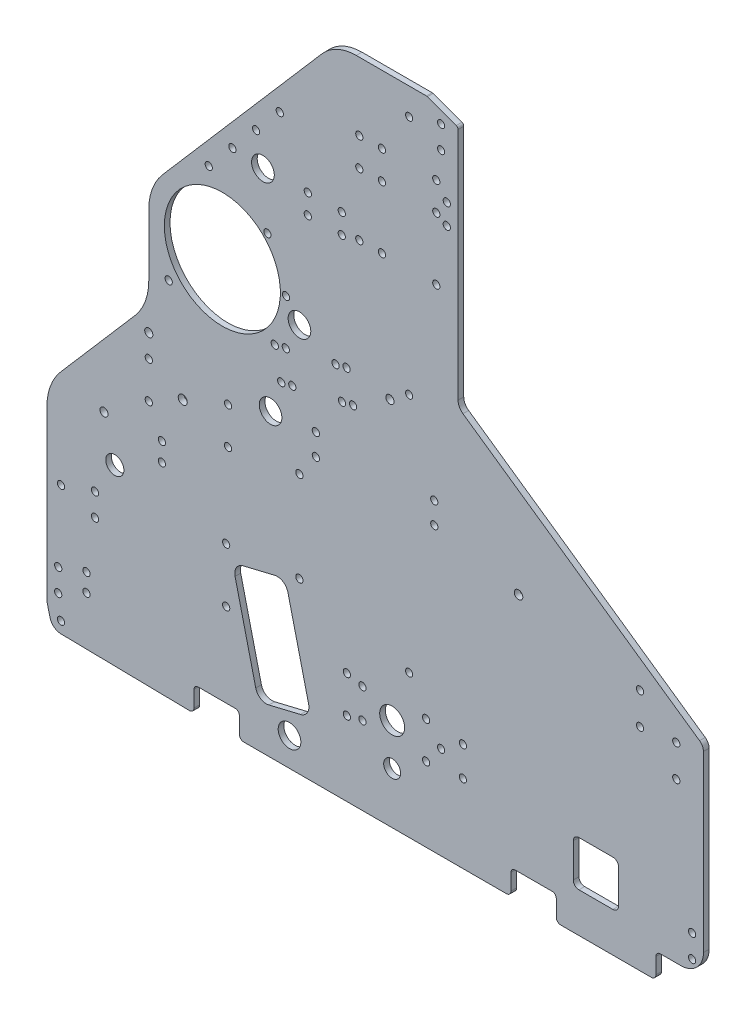
SolidWorks part; units mm, degrees
ref_plane "Front Plane" through (0, 0, 0) normal (0, 0, 1) x (1, 0, 0)
ref_plane "Top Plane" through (0, 0, 0) normal (0, 1, 0) x (1, 0, 0)
ref_plane "Right Plane" through (0, 0, 0) normal (1, 0, 0) x (0, 0, -1)
sketch "Sketch1" plane through (0, 0, 0) normal (0, 0, 1) x (1, 0, 0)
  line L0 (82.55, -20.32) -> (82.55, -6.35)
  line L2 (0, 0) -> (0, 157.48)
  line L4 (368.3, -20.32) -> (368.3, 106.68)
  line L5 (82.55, -6.35) -> (107.95, -6.35)
  line L6 (107.95, -6.35) -> (107.95, -20.32)
  line L7 (107.95, -20.32) -> (260.35, -20.32)
  line L8 (260.35, -20.32) -> (260.35, -6.35)
  line L9 (260.35, -6.35) -> (285.75, -6.35)
  line L10 (285.75, -6.35) -> (285.75, -20.32)
  line L11 (285.75, -20.32) -> (368.3, -20.32)
  line L12 (361.95, 12.7) -> (368.3, 12.7) construction
  line L13 (0, 0) -> (6.35, 0) construction
  line L14 (0.1896, -7.8901) -> (1.7771, -14.2401)
  line L15 (7.8295, -19.0491) -> (82.55, -20.32)
  line L16 (0, 0) -> (0, -6.35)
  line L17 (76.2, 128.905) -> (79.375, 128.905) construction
  line L18 (57.15, 118.5863) -> (101.6, 118.5862) construction
  line L19 (57.15, 118.5863) -> (57.15, 139.2238) construction
  line L20 (101.6, 118.5862) -> (101.6, 139.2237) construction
  line L21 (57.15, 139.2238) -> (101.6, 139.2237) construction
  line L22 (57.15, 118.5863) -> (101.6, 139.2237) construction
  line L23 (101.6, 118.5862) -> (57.15, 139.2238) construction
  line L24 (101.6, 139.2237) -> (125.4682, 147.9111) construction
  line L25 (203.2, 59.805) -> (203.2, 194.805) construction
  line L26 (203.2, 194.805) -> (203.2, 329.805) construction
  line L27 (355.6, 332.105) -> (330.2, 332.105) construction
  line L28 (330.2, 332.105) -> (330.2, 217.805) construction
  line L29 (330.2, 217.805) -> (355.6, 217.805) construction
  line L30 (355.6, 217.805) -> (355.6, 332.105) construction
  line L31 (203.2, 344.805) -> (203.2, 194.805) construction
  line L32 (50.8, 332.105) -> (76.2, 332.105) construction
  line L33 (76.2, 332.105) -> (76.2, 217.805) construction
  line L34 (50.8, 217.805) -> (50.8, 332.105) construction
  line L35 (76.2, 217.805) -> (50.8, 217.805) construction
  line L36 (213.2, 344.805) -> (230.6638, 338.455)
  line L37 (203.2, 344.805) -> (161.925, 344.805)
  line L38 (203.2, 344.805) -> (213.2, 344.805)
  line L39 (348.5362, 344.805) -> (413.4623, 344.805)
  line L40 (348.5362, 344.805) -> (230.6638, 344.805) construction
  line L42 (161.925, 344.805) -> (0, 157.48)
  line L44 (230.6638, 338.455) -> (230.6638, 202.565)
  line L45 (230.6638, 202.565) -> (368.3, 106.68)
  line L46 (213.2, 344.805) -> (-141.0713, 344.805) construction
  circle A0 centre (6.35, 0) radius 2.032
  circle A1 centre (6.35, 12.7) radius 2.032
  circle A2 centre (361.95, 0) radius 2.032
  circle A3 centre (361.95, 12.7) radius 2.032
  arc A5 (1.7771, -14.2401) -> (7.8295, -19.0491) centre (7.9375, -12.7) ccw
  circle A6 centre (7.9375, -12.7) radius 2.032
  arc A7 (0, -6.35) -> (0.1896, -7.8901) centre (6.35, -6.35) ccw
  circle A8 centre (38.1, 78.105) radius 5.08
  circle A9 centre (76.2, 128.905) radius 2.54
  circle A10 centre (101.6, 118.5862) radius 2.032
  circle A11 centre (101.6, 139.2237) radius 2.032
  circle A12 centre (57.15, 139.2238) radius 2.032
  circle A13 centre (57.15, 118.5863) radius 2.032
  circle A15 centre (203.2, 59.805) radius 2
  circle A16 centre (203.2, 194.805) radius 2
  circle A17 centre (203.2, 329.805) radius 2
  circle A18 centre (63.5, 313.055) radius 2.032
  circle A20 centre (355.6, 332.105) radius 2.032
  circle A21 centre (330.2, 332.105) radius 2.032
  circle A22 centre (355.6, 217.805) radius 2.032
  circle A23 centre (330.2, 217.805) radius 2.032
  circle A24 centre (50.8, 332.105) radius 2.032
  circle A25 centre (76.2, 332.105) radius 2.032
  circle A26 centre (50.8, 217.805) radius 2.032
  circle A27 centre (76.2, 217.805) radius 2.032
  circle A28 centre (221.1381, 335.28) radius 2
  circle A29 centre (224.3138, 298.831) radius 2.032
  circle A30 centre (353.06, 100.7351) radius 2.032
  circle A31 centre (332.74, 115.9751) radius 2.032
  circle A32 centre (332.74, 98.1951) radius 2.032
  circle A33 centre (353.06, 82.9551) radius 2.032
  circle A34 centre (117.3562, 280.4276) radius 2.032
  circle A35 centre (104.0678, 265.0548) radius 2.032
  circle A36 centre (90.7795, 249.682) radius 2.032
  circle A38 centre (130.6445, 295.8004) radius 2.032
  circle A39 centre (68.326, 182.9237) radius 2.032
  circle A40 centre (224.3138, 287.401) radius 2.032
  circle A41 centre (125.4682, 147.9111) radius 6.35
  circle A42 centre (221.1381, 322.58) radius 2
  point P82 (203.2, 344.805)
  point P90 (368.3, 62.484)
  point P106 (0, 0)
  dimension "D6" = 4.064
  dimension "D10" = 6.35
  dimension "D11" = 4.064
  dimension "D17" = 38.1
  dimension "D27" = 4
  dimension "D31" = 4.064
  dimension "D32" = 41.275
  dimension "D36" = 4.064
  dimension "D47" = 39.624
  dimension "D48" = 4.064
  dimension "D25" = 5.08
  dimension "D26" = 4.064
  dimension "D52" = 4.064
  dimension "D65" = 4.064
  dimension "D69" = 10.16
  dimension "D72" = 12.7
  dimension "D2" = 127
  dimension "D3" = 13.97
  dimension "D4" = 25.4
  dimension "D5" = 152.4
  dimension "D7" = 12.7
  dimension "D8" = 6.35
  dimension "D9" = 20.32
  dimension "D12" = 12.7
  dimension "D13" = 1.5875
  dimension "D14" = 82.55
  dimension "D15" = 368.3
  dimension "D16" = 6.35
  dimension "D18" = 98.425
  dimension "D19" = 38.1
  dimension "D20" = 50.8
  dimension "D21" = 3.175
  dimension "D22" = 270
  dimension "D23" = 20.6375
  dimension "D24" = 44.45
  dimension "D28" = 135
  dimension "D29" = 12.7
  dimension "D30" = 15
  dimension "D33" = 63.5
  dimension "D34" = 27.4638
  dimension "D35" = 12.7
  dimension "D37" = 114.3
  dimension "D38" = 25.4
  dimension "D39" = 12.7
  dimension "D40" = 157.48
  dimension "D41" = 142.24
  dimension "D42" = 365.125
  dimension "D43" = 10
  dimension "D44" = 6.35
  dimension "D45" = 31.75
  dimension "D46" = 3.175
  dimension "D49" = 6.35
  dimension "D50" = 203.2
  dimension "D51" = 15.24
  dimension "D53" = 17.78
  dimension "D54" = 17.78
  dimension "D55" = 20.32
  dimension "D56" = 15.24
  dimension "D57" = 92.202
  dimension "D58" = 8.382
  dimension "D59" = 20.32
  dimension "D60" = 20.32
  dimension "D61" = 8.382
  dimension "D62" = 20.32
  dimension "D63" = 8.382
  dimension "D64" = 8.382
  dimension "D66" = 35.052
  dimension "D67" = 68.326
  dimension "D68" = 11.43
  dimension "D70" = 25.4
  dimension "D71" = 110
  dimension "D73" = 17.9381
  dimension "D74" = 12.7
extrude "Boss-Extrude1" add sketch "Sketch1" along normal blind 3.175 contours L16 A7 L14 A5 L15 L2 A0 A1 A6 region at (171.5045, 119.4976, 0)
fillet "Fillet1" radius 2.286 4 edges at (285.75, -6.35, 1.5875) (107.95, -6.35, 1.5875) (260.35, -6.35, 1.5875) (82.55, -6.35, 1.5875)
fillet "Fillet2" radius 6.35 1 edges at (230.6638, 202.565, 1.5875)
sketch "Sketch2" plane through (0, 0, 0) normal (0, 0, -1) x (-1, 0, 0)
  circle A0 centre (-100.5528, 71.086) radius 2.032 construction
  circle A1 centre (-100.5528, 40.606) radius 2.032 construction
  circle A2 centre (-22.225, 18.2025) radius 2.032 construction
  circle A3 centre (-22.225, 8.0425) radius 2.032 construction
  circle A4 centre (-100.5528, 71.086) radius 2.032
  circle A5 centre (-100.5528, 40.606) radius 2.032
  circle A6 centre (-22.225, 18.2025) radius 2.032
  circle A7 centre (-22.225, 8.0425) radius 2.032
extrude "Cut-Extrude1" cut sketch "Sketch2" against normal through all
fillet "Fillet3" radius 1.5875 2 edges at (230.6638, 338.455, 1.5875) (213.2, 344.805, 1.5875)
sketch "Sketch3" plane through (0, 0, 3.175) normal (0, 0, 1) x (1, 0, 0)
  line L0 (132.9524, 63.2646) -> (132.7215, 64.2281) construction
  line L1 (128.3814, 66.8897) -> (110.6828, 62.6472) construction
  line L2 (114.5132, 58.4237) -> (126.8822, 61.3887) construction
  line L3 (108.0212, 58.3071) -> (108.2522, 57.3436) construction
  line L4 (131.2006, 57.703) -> (140.0164, 20.9265) construction
  line L5 (144.0993, 16.7636) -> (132.9524, 63.2646) construction
  line L6 (108.2522, 57.3436) -> (119.3991, 10.8426) construction
  line L7 (121.1509, 16.4042) -> (112.3351, 53.1807) construction
  line L8 (119.3991, 10.8426) -> (119.6301, 9.8791) construction
  line L9 (144.3303, 15.8001) -> (144.0993, 16.7636) construction
  line L10 (137.8383, 15.6835) -> (125.4694, 12.7185) construction
  line L11 (123.9701, 7.2175) -> (141.6687, 11.4601) construction
  line L12 (132.9524, 63.2646) -> (132.7215, 64.2281)
  line L13 (128.3814, 66.8897) -> (110.6828, 62.6472)
  line L14 (114.5132, 58.4237) -> (126.8822, 61.3887)
  line L15 (108.0212, 58.3071) -> (108.2522, 57.3436)
  line L16 (131.2006, 57.703) -> (140.0164, 20.9265)
  line L17 (144.0993, 16.7636) -> (132.9524, 63.2646)
  line L18 (108.2522, 57.3436) -> (119.3991, 10.8426)
  line L19 (121.1509, 16.4042) -> (112.3351, 53.1807)
  line L20 (119.3991, 10.8426) -> (119.6301, 9.8791)
  line L21 (144.3303, 15.8001) -> (144.0993, 16.7636)
  line L22 (137.8383, 15.6835) -> (125.4694, 12.7185)
  line L23 (123.9701, 7.2175) -> (141.6687, 11.4601)
  line L24 (127.7894, 69.3598) -> (110.0908, 65.1172)
  line L25 (105.5512, 57.715) -> (105.7822, 56.7515)
  line L26 (105.7822, 56.7515) -> (116.9291, 10.2505)
  line L27 (116.9291, 10.2505) -> (117.16, 9.287)
  line L28 (124.5622, 4.7475) -> (142.2608, 8.99)
  line L29 (146.8003, 16.3922) -> (146.5694, 17.3557)
  line L30 (146.5694, 17.3557) -> (135.4225, 63.8567)
  line L31 (135.4225, 63.8567) -> (135.1915, 64.8202)
  line L32 (14.605, -0.1369) -> (103.7278, 32.3011) construction
  line L33 (14.605, -0.1369) -> (103.7278, 32.3011)
  line L34 (0, -6.35) -> (0, 157.48) construction
  line L35 (-39.6666, 74.7152) -> (103.7278, 126.9065) construction
  line L36 (26.9875, 46.9531) -> (26.9875, 59.6531) construction
  line L37 (107.95, -20.32) -> (260.35, -20.32) construction
  line L38 (64.5259, 92.5258) -> (64.5259, 102.9405) construction
  line L39 (131.6538, 14.201) -> (136.0946, -4.3242) construction
  arc A0 (132.7215, 64.2281) -> (128.6308, 66.9403) centre (129.2206, 63.3889) ccw construction
  arc A1 (110.6828, 62.6472) -> (110.4377, 62.5791) centre (111.522, 59.1463) ccw construction
  arc A2 (128.6308, 66.9403) -> (128.3814, 66.8897) centre (129.2206, 63.3889) ccw construction
  arc A3 (110.4377, 62.5791) -> (108.0212, 58.3071) centre (111.522, 59.1463) ccw construction
  arc A4 (119.6301, 9.8791) -> (123.7207, 7.1669) centre (123.1309, 10.7183) ccw construction
  arc A5 (141.9139, 11.5281) -> (144.3303, 15.8001) centre (140.8295, 14.9609) ccw construction
  arc A6 (141.6687, 11.4601) -> (141.9139, 11.5281) centre (140.8295, 14.9609) ccw construction
  arc A7 (123.7207, 7.1669) -> (123.9701, 7.2175) centre (123.1309, 10.7183) ccw construction
  arc A8 (132.7215, 64.2281) -> (128.6308, 66.9403) centre (129.2206, 63.3889) ccw
  arc A9 (110.6828, 62.6472) -> (110.4377, 62.5791) centre (111.522, 59.1463) ccw
  arc A10 (128.6308, 66.9403) -> (128.3814, 66.8897) centre (129.2206, 63.3889) ccw
  arc A11 (110.4377, 62.5791) -> (108.0212, 58.3071) centre (111.522, 59.1463) ccw
  arc A12 (119.6301, 9.8791) -> (123.7207, 7.1669) centre (123.1309, 10.7183) ccw
  arc A13 (141.9139, 11.5281) -> (144.3303, 15.8001) centre (140.8295, 14.9609) ccw
  arc A14 (141.6687, 11.4601) -> (141.9139, 11.5281) centre (140.8295, 14.9609) ccw
  arc A15 (123.7207, 7.1669) -> (123.9701, 7.2175) centre (123.1309, 10.7183) ccw
  arc A16 (110.0908, 65.1172) -> (109.6726, 65.0012) centre (111.522, 59.1463) ccw
  arc A17 (109.6726, 65.0012) -> (105.5512, 57.715) centre (111.522, 59.1463) ccw
  arc A18 (117.16, 9.287) -> (124.1369, 4.6613) centre (123.1309, 10.7183) ccw
  arc A19 (124.1369, 4.6613) -> (124.5622, 4.7475) centre (123.1309, 10.7183) ccw
  arc A20 (142.2608, 8.99) -> (142.6789, 9.1061) centre (140.8295, 14.9609) ccw
  arc A21 (142.6789, 9.1061) -> (146.8003, 16.3922) centre (140.8295, 14.9609) ccw
  arc A22 (135.1915, 64.8202) -> (128.2147, 69.446) centre (129.2206, 63.3889) ccw
  arc A23 (128.2147, 69.446) -> (127.7894, 69.3598) centre (129.2206, 63.3889) ccw
  circle A24 centre (136.0946, -4.3242) radius 6.35
  circle A26 centre (134.1437, 208.2281) radius 2.032 construction
  circle A33 centre (26.9875, 46.9531) radius 2.032
  circle A34 centre (26.9875, 59.6531) radius 2.032
  circle A35 centre (7.9375, 53.3031) radius 2.032
  circle A37 centre (32.0306, 100.8109) radius 32.385 construction
  circle A38 centre (32.0306, 100.8109) radius 2.286
  circle A39 centre (123.682, 233.4851) radius 2.032 construction
  circle A40 centre (64.5259, 102.9405) radius 2.032
  circle A41 centre (64.5259, 92.5258) radius 2.032
  circle A42 centre (134.1437, 208.2281) radius 2.032
  circle A43 centre (123.682, 233.4851) radius 2.032
  ellipse E0 centre (124.5974, 48.8487) end of major axis (128.5376, 61.3578) minor radius 6 (131.2006, 57.703) -> (126.8822, 61.3887) ccw construction
  ellipse E1 centre (122.2349, 48.2824) end of major axis (113.0518, 57.6456) minor radius 6 (114.5132, 58.4237) -> (112.3351, 53.1807) ccw construction
  ellipse E2 centre (127.7541, 25.2585) end of major axis (131.6942, 37.7675) minor radius 6 (121.1509, 16.4042) -> (125.4694, 12.7185) ccw construction
  ellipse E3 centre (130.1166, 25.8248) end of major axis (139.2998, 16.4616) minor radius 6 (137.8383, 15.6835) -> (140.0164, 20.9265) ccw construction
  ellipse E4 centre (124.5974, 48.8487) end of major axis (120.6573, 36.3397) minor radius 6 (131.2006, 57.703) -> (126.8822, 61.3887) ccw
  ellipse E5 centre (122.2349, 48.2824) end of major axis (131.4181, 38.9192) minor radius 6 (114.5132, 58.4237) -> (112.3351, 53.1807) ccw
  ellipse E6 centre (127.7541, 25.2585) end of major axis (131.6942, 37.7675) minor radius 6 (121.1509, 16.4042) -> (125.4694, 12.7185) ccw
  ellipse E7 centre (130.1166, 25.8248) end of major axis (139.2998, 16.4616) minor radius 6 (137.8383, 15.6835) -> (140.0164, 20.9265) ccw
  point P93 (26.9875, 53.3031)
  point P115 (32.0306, 100.8109)
  dimension "D3" = 64.77
  dimension "D4" = 4.572
  dimension "D8" = 4.064
  dimension "D13" = 12.7
  dimension "D2" = 88.9
  dimension "D5" = 7.9375
  dimension "D6" = 19.05
  dimension "D7" = 73.6231
  dimension "D9" = 12.7
  dimension "D10" = 10.4147
  dimension "D11" = 37.5384
  dimension "D12" = 45.5727
  dimension "D14" = 19.05
  dimension "D1" = 2.54
extrude "Cut-Extrude2" cut sketch "Sketch3" against normal through all contours A22 A23 L24 A16 A17 L25 L26 L27 A18 A19 L28 A20 A21 L29 L30 L31 A15 A12 L20 L18 L15 A11 A9 L13 A10 A8 L12 L17 L21 A13 A14 L23 | A12 A15 L23 A14 A13 L21 L17 L12 A8 A10 L13 A9 A11 L15 L18 L20 E7 L22 E6 L19 E5 L14 E4 L16 | L22 E7 L16 E4 L14 E5 L19 E6 | A38 | A41 | A40 | A35 | A34 | A33 | A43 | A42 | A24 region at (137.844, 39.8506, 3.175) region at (126.1758, 37.0536, 3.175) region at (128.1544, 68.6507, 3.175) region at (32.0306, 100.8109, 3.175) region at (64.5259, 102.9405, 3.175) region at (64.5259, 92.5258, 3.175)
sketch "Sketch4" plane through (0, 0, 3.175) normal (0, 0, 1) x (1, 0, 0)
  line L0 (57.15, 139.2238) -> (101.6, 139.2237) construction
  line L1 (168.275, 21.4312) -> (212.725, 21.4312) construction
  line L2 (168.275, 21.4312) -> (168.275, 42.0687) construction
  line L3 (168.275, 42.0687) -> (212.725, 42.0687) construction
  line L4 (212.725, 21.4312) -> (212.725, 42.0687) construction
  line L5 (168.275, 21.4312) -> (212.725, 42.0687) construction
  line L6 (168.275, 42.0687) -> (212.725, 21.4312) construction
  line L7 (57.15, 118.5863) -> (57.15, 139.2238) construction
  line L8 (107.95, -20.32) -> (260.35, -20.32) construction
  line L9 (193.675, 31.75) -> (177.005, 31.75) construction
  line L10 (190.5, 31.75) -> (193.675, 31.75) construction
  line L11 (6.35, 12.7) -> (361.95, 12.7) construction
  line L12 (107.95, -6.35) -> (107.95, -20.32) construction
  line L13 (193.675, 31.75) -> (220.6625, 31.75) construction
  line L14 (177.005, 23.4569) -> (177.005, 40.0431) construction
  line L15 (213.2, 44.805) -> (193.2, 44.805) construction
  line L16 (213.2, 44.805) -> (213.2, 344.805) construction
  line L17 (213.2, 344.805) -> (193.2, 344.805) construction
  line L18 (193.2, 44.805) -> (193.2, 344.805) construction
  line L19 (213.2, 44.805) -> (193.2, 344.805) construction
  line L20 (213.2, 344.805) -> (193.2, 44.805) construction
  line L21 (226.1381, 335.28) -> (226.1381, 31.75) construction
  line L22 (237.33, 40.0431) -> (233.3612, 40.0431) construction
  line L23 (237.33, 23.4569) -> (233.3612, 23.4569) construction
  circle A0 centre (168.275, 42.0687) radius 2.032
  circle A1 centre (212.725, 42.0687) radius 2.032
  circle A2 centre (212.725, 21.4312) radius 2.032
  circle A3 centre (168.275, 21.4312) radius 2.032
  circle A4 centre (193.675, 31.75) radius 6.985
  circle A7 centre (220.6625, 31.75) radius 14.2875 construction
  circle A8 centre (193.675, 31.75) radius 12.7 construction
  circle A9 centre (177.005, 40.0431) radius 2.032
  circle A10 centre (177.005, 23.4569) radius 2.032
  circle A11 centre (237.33, 40.0431) radius 2.032 construction
  circle A12 centre (237.33, 23.4569) radius 2.032 construction
  circle A13 centre (193.675, 8.4667) radius 4.7625
  circle A14 centre (221.1381, 31.75) radius 2.032
  circle A15 centre (221.1381, 31.75) radius 5 construction
  circle A16 centre (221.1381, 335.28) radius 5 construction
  circle A17 centre (233.3612, 23.4569) radius 2.032
  circle A18 centre (233.3612, 40.0431) radius 2.032
  point P0 (190.5, 31.75)
  point P26 (203.2, 194.805)
  point P38 (177.005, 31.75)
  dimension "D1" = 4.064
  dimension "D4" = 13.97
  dimension "D7" = 9.525
  dimension "D10" = 25.4
  dimension "D11" = 28.575
  dimension "D16" = 10
  dimension "D17" = 4.064
  dimension "D18" = 10
  dimension "D2" = 52.07
  dimension "D3" = 3.175
  dimension "D5" = 82.55
  dimension "D6" = 26.9875
  dimension "D8" = 20
  dimension "D9" = 300
  dimension "D12" = 16.67
  dimension "D13" = 16.5862
  dimension "D14" = 60.325
  dimension "D15" = 23.2833
  dimension "D19" = 3.9688
extrude "Cut-Extrude3" cut sketch "Sketch4" against normal through all
sketch "Sketch5" plane through (0, 0, 0) normal (0, 0, -1) x (-1, 0, 0)
  line L0 (-57.15, 223.5947) -> (-57.15, 165.3337)
  line L1 (-161.925, 344.805) -> (-52.7201, 218.4699) construction
  line L2 (-57.15, 165.3337) -> (0, 99.219)
  line L3 (0, -6.35) -> (0, 157.48) construction
  line L4 (-147.864, -30.311) -> (-147.864, -16.0874)
  line L5 (-50.4199, 215.8089) -> (0, 157.48) construction
  line L6 (-57.15, 223.5947) -> (0, 157.48)
  line L7 (0, 157.48) -> (0, 99.219)
  line L8 (-98.425, 208.2281) -> (-141.6756, 197.9719) construction
  line L10 (-341.63, -6.35) -> (-341.63, -21.2964)
  line L12 (-371.0782, -6.35) -> (-341.63, -6.35)
  line L13 (-285.75, -20.32) -> (-368.3, -20.32) construction
  line L14 (-371.0782, -6.35) -> (-371.0782, -21.2964)
  line L15 (-371.0782, -21.2964) -> (-341.63, -21.2964)
  circle A0 centre (-98.425, 208.2281) radius 32.5437
  circle A1 centre (-141.6756, 197.9719) radius 6.35
  circle A3 centre (-264.5736, 128.3328) radius 2.39
  dimension "D3" = 65.0875
  dimension "D7" = 12.7
  dimension "D8" = 4.78
  dimension "D1" = 38.1
  dimension "D2" = 57.15
  dimension "D4" = 41.275
  dimension "D5" = 41.275
  dimension "D6" = 13.97
  dimension "D9" = 22.2382
  dimension "D10" = 117.7733
  dimension "D11" = 11.6447
  dimension "D12" = 123.5853
  dimension "D14" = 62.5
  dimension "D13" = 44.45
extrude "Cut-Extrude5" cut sketch "Sketch5" against normal through all contours A0 | L7 L6 L0 L2 | A3 | L14 L15 L10 L12 | A1 region at (28.575, 161.4068, 0) region at (356.3541, -13.8232, 0) region at (98.425, 208.2281, 0) region at (264.5736, 128.3328, 0)
fillet "Fillet4" radius 31.75 3 edges at (0, 99.219, 1.5875) (57.15, 165.3337, 1.5875) (57.15, 223.5947, 1.5875)
sketch "Sketch6" plane through (0, 0, 3.175) normal (0, 0, 1) x (1, 0, 0)
  line L0 (285.75, -20.32) -> (341.63, -20.32) construction
  line L1 (298.45, 27.305) -> (317.5, 27.305)
  line L2 (295.275, 24.13) -> (295.275, 5.08)
  line L3 (298.45, 1.905) -> (317.5, 1.905)
  line L4 (320.675, 24.13) -> (320.675, 5.08)
  line L5 (295.275, 27.305) -> (320.675, 1.905) construction
  line L6 (295.275, 1.905) -> (320.675, 27.305) construction
  line L7 (368.3, -6.35) -> (368.3, 106.68) construction
  arc A0 (295.275, 5.08) -> (298.45, 1.905) centre (298.45, 5.08) ccw
  arc A1 (317.5, 1.905) -> (320.675, 5.08) centre (317.5, 5.08) ccw
  arc A2 (317.5, 27.305) -> (320.675, 24.13) centre (317.5, 24.13) cw
  arc A3 (298.45, 27.305) -> (295.275, 24.13) centre (298.45, 24.13) ccw
  point P0 (307.975, 14.605)
  dimension "D2" = 3.175
  dimension "D1" = 25.4
  dimension "D3" = 22.225
  dimension "D4" = 47.625
extrude "Cut-Extrude6" cut sketch "Sketch6" against normal through all
fillet "Fillet5" radius 25.4 1 edges at (161.925, 344.805, 1.5875)
sketch "Sketch8" plane through (0, 0, 0) normal (0, 0, -1) x (-1, 0, 0)
  line L0 (-230.6638, 337.343) -> (-230.6638, 205.8802) construction
  line L1 (-230.6638, 255.905) -> (-175.26, 255.905) construction
  line L2 (-175.26, 255.905) -> (-175.26, 306.705) construction
  line L3 (-175.26, 306.705) -> (-230.6638, 306.705) construction
  line L4 (-173.5432, 344.805) -> (-212.9203, 344.805) construction
  line L7 (-107.95, -20.32) -> (-260.35, -20.32) construction
  circle A0 centre (-218.44, 290.83) radius 3.9687
  circle A1 centre (-218.44, 290.83) radius 2.032
  circle A2 centre (218.44, 265.7972) radius 3.9687
  circle A3 centre (218.44, 265.7972) radius 2.032
  circle A4 centre (-205.74, 290.83) radius 3.9687
  circle A5 centre (-205.74, 290.83) radius 2.032
  circle A6 centre (-187.96, 290.83) radius 3.9687
  circle A7 centre (-187.96, 290.83) radius 2.032
  circle A8 centre (-187.96, 306.705) radius 2.032
  circle A9 centre (-175.26, 290.83) radius 3.9687
  circle A10 centre (-175.26, 290.83) radius 2.032
  circle A11 centre (-205.74, 306.705) radius 2.032
  circle A13 centre (-205.74, 255.905) radius 2.032
  circle A14 centre (-187.96, 255.905) radius 2.032
  circle A16 centre (-218.44, 306.705) radius 2.032
  circle A17 centre (-175.26, 306.705) radius 2.032
  circle A18 centre (-175.26, 255.905) radius 2.032
  circle A19 centre (-218.44, 255.905) radius 2.032
  circle A20 centre (-218.44, 306.705) radius 3.9687
  circle A21 centre (-205.74, 306.705) radius 3.9687
  circle A22 centre (-175.26, 306.705) radius 3.9687
  circle A23 centre (-218.44, 255.905) radius 3.9687
  circle A24 centre (-205.74, 255.905) radius 3.9687
  circle A25 centre (-187.96, 255.905) radius 3.9687
  circle A26 centre (-175.26, 255.905) radius 3.9687
  circle A27 centre (-187.96, 306.705) radius 3.9687
  dimension "D1" = 7.9375
  dimension "D7" = 4.064
  dimension "D13" = 12.2237
  dimension "D2" = 12.2237
  dimension "D3" = 12.7
  dimension "D4" = 17.78
  dimension "D5" = 12.7
  dimension "D6" = 88.9
  dimension "D8" = 38.1
  dimension "D9" = 17.78
  dimension "D10" = 12.7
  dimension "D11" = 55.4037
  dimension "D12" = 12.7
  dimension "D14" = 311.15
extrude "Cut-Extrude7" cut sketch "Sketch8" against normal through all contours A16 | A17 | A18 | A19 | A8 | A14 | A1 | A7 | A10 region at (218.44, 306.705, 0) region at (175.26, 306.705, 0) region at (175.26, 255.905, 0) region at (218.44, 255.905, 0)
sketch "Sketch10" plane through (0, 0, 3.175) normal (0, 0, 1) x (1, 0, 0)
  circle A4 centre (141.6425, 74.6844) radius 2.032 construction
  circle A5 centre (141.6425, 125.4844) radius 2.032 construction
  circle A6 centre (141.6425, 74.6844) radius 2.032
  circle A7 centre (141.6425, 125.4844) radius 2.032
extrude "Cut-Extrude8" cut sketch "Sketch10" against normal through all
sketch "Sketch11" plane through (0, 0, 3.175) normal (0, 0, 1) x (1, 0, 0)
  ellipse E4 centre (150.8814, 138.43) end of major axis (150.8814, 140.462) minor radius 2.032
  ellipse E5 centre (150.8814, 150.495) end of major axis (150.8814, 152.527) minor radius 2.032
  ellipse E6 centre (217.3024, 150.495) end of major axis (217.3024, 152.527) minor radius 2.032
  ellipse E7 centre (217.3024, 138.43) end of major axis (217.3024, 140.462) minor radius 2.032
extrude "Cut-Extrude9" cut sketch "Sketch11" against normal through all
sketch "Sketch12" plane through (0, 0, 0) normal (0, 0, -1) x (-1, 0, 0)
  line L0 (-173.5432, 344.805) -> (-212.9203, 344.805) construction
  circle A0 centre (-165.4175, 264.635) radius 2.032
  circle A1 centre (-203.2, 329.805) radius 2 construction
  circle A2 centre (-165.4175, 253.5225) radius 2.032
  circle A3 centre (-146.3675, 253.5225) radius 2.032
  circle A4 centre (-146.3675, 264.635) radius 2.032
  dimension "D1" = 80.17
  dimension "D2" = 4.064
  dimension "D3" = 37.7825
  dimension "D4" = 11.1125
  dimension "D5" = 19.05
extrude "Cut-Extrude10" cut sketch "Sketch12" against normal through all
sketch "Sketch14" plane through (0, 0, 0) normal (0, 0, -1) x (-1, 0, 0)
  line L0 (-130.6445, 295.8004) -> (-121.1847, 263.6885) construction
  line L1 (-121.1847, 263.6885) -> (-90.7795, 249.682) construction
  line L2 (-154.3272, 336.0154) -> (-64.88, 232.5373) construction
  line L4 (-118.517, 269.4796) -> (-115.3937, 261.0208) construction
  line L5 (-118.517, 269.4796) -> (-126.9758, 266.3562) construction
  line L6 (-126.9758, 266.3562) -> (-123.8524, 257.8974) construction
  line L7 (-115.3937, 261.0208) -> (-123.8524, 257.8974) construction
  line L8 (-118.517, 269.4796) -> (-123.8524, 257.8974) construction
  line L9 (-126.9758, 266.3562) -> (-115.3937, 261.0208) construction
  circle A0 centre (-121.1847, 263.6885) radius 6.376
  dimension "D1" = 22.225
  dimension "D2" = 9.017
extrude "Cut-Extrude11" cut sketch "Sketch14" against normal through all
sketch "Sketch15" plane through (0, 0, 3.175) normal (0, 0, 1) x (1, 0, 0)
  line L1 (27.1508, 77.7471) -> (81.7263, 77.7471) construction
  line L2 (57.15, 139.2238) -> (57.15, 151.9238) construction
  line L3 (27.1508, 77.7471) -> (52.3291, 153.5255) construction
  line L4 (56.0505, 156.8833) -> (192.439, 187.1199) construction
  circle A0 centre (27.1508, 77.7471) radius 2.159 construction
  circle A1 centre (27.1508, 77.7471) radius 2.159 construction
  circle A2 centre (57.15, 139.2238) radius 2.032 construction
  circle A3 centre (57.15, 139.2238) radius 2.032 construction
  circle A4 centre (57.15, 151.9238) radius 2.286
  circle A5 centre (192.439, 187.1199) radius 2.286
  circle A6 centre (57.15, 151.9238) radius 5.08 construction
  arc A9 (163.8737, 173.6806) -> (164.5125, 170.7993) centre (165.557, 172.5423) ccw construction
  arc A10 (173.4398, 172.7784) -> (172.801, 175.6597) centre (171.7565, 173.9167) ccw construction
  arc A11 (172.801, 175.6597) -> (173.4398, 172.7784) centre (171.7565, 173.9167) ccw construction
  arc A12 (164.5125, 170.7993) -> (163.8737, 173.6806) centre (165.557, 172.5423) ccw construction
  arc A13 (169.1589, 192.0883) -> (169.7976, 189.2071) centre (168.1143, 190.3453) ccw construction
  arc A14 (169.7976, 189.2071) -> (169.1589, 192.0883) centre (168.1143, 190.3453) ccw construction
  arc A15 (160.2316, 190.1092) -> (160.8704, 187.2279) centre (161.9149, 188.9709) ccw construction
  arc A16 (160.8704, 187.2279) -> (160.2316, 190.1092) centre (161.9149, 188.9709) ccw construction
  arc A17 (129.7766, 166.1214) -> (130.4154, 163.2402) centre (131.4599, 164.9832) ccw construction
  arc A18 (139.3426, 165.2193) -> (138.7039, 168.1005) centre (137.6593, 166.3576) ccw construction
  arc A19 (138.7039, 168.1005) -> (139.3426, 165.2193) centre (137.6593, 166.3576) ccw construction
  arc A20 (130.4154, 163.2402) -> (129.7766, 166.1214) centre (131.4599, 164.9832) ccw construction
  arc A21 (135.7005, 181.6479) -> (135.0617, 184.5292) centre (134.0172, 182.7862) ccw construction
  arc A22 (135.0617, 184.5292) -> (135.7005, 181.6479) centre (134.0172, 182.7862) ccw construction
  arc A23 (126.1345, 182.55) -> (126.7732, 179.6688) centre (127.8177, 181.4118) ccw construction
  arc A24 (126.7732, 179.6688) -> (126.1345, 182.55) centre (127.8177, 181.4118) ccw construction
  arc A25 (163.8737, 173.6806) -> (164.5125, 170.7993) centre (165.557, 172.5423) ccw
  arc A26 (173.4398, 172.7784) -> (172.801, 175.6597) centre (171.7565, 173.9167) ccw
  arc A27 (172.801, 175.6597) -> (173.4398, 172.7784) centre (171.7565, 173.9167) ccw
  arc A28 (164.5125, 170.7993) -> (163.8737, 173.6806) centre (165.557, 172.5423) ccw
  arc A29 (169.1589, 192.0883) -> (169.7976, 189.2071) centre (168.1143, 190.3453) ccw
  arc A30 (169.7976, 189.2071) -> (169.1589, 192.0883) centre (168.1143, 190.3453) ccw
  arc A31 (160.2316, 190.1092) -> (160.8704, 187.2279) centre (161.9149, 188.9709) ccw
  arc A32 (160.8704, 187.2279) -> (160.2316, 190.1092) centre (161.9149, 188.9709) ccw
  arc A33 (129.7766, 166.1214) -> (130.4154, 163.2402) centre (131.4599, 164.9832) ccw
  arc A34 (139.3426, 165.2193) -> (138.7039, 168.1005) centre (137.6593, 166.3576) ccw
  arc A35 (138.7039, 168.1005) -> (139.3426, 165.2193) centre (137.6593, 166.3576) ccw
  arc A36 (130.4154, 163.2402) -> (129.7766, 166.1214) centre (131.4599, 164.9832) ccw
  arc A37 (135.7005, 181.6479) -> (135.0617, 184.5292) centre (134.0172, 182.7862) ccw
  arc A38 (135.0617, 184.5292) -> (135.7005, 181.6479) centre (134.0172, 182.7862) ccw
  arc A39 (126.1345, 182.55) -> (126.7732, 179.6688) centre (127.8177, 181.4118) ccw
  arc A40 (126.7732, 179.6688) -> (126.1345, 182.55) centre (127.8177, 181.4118) ccw
  dimension "D2" = 4.572
  dimension "D6" = 10.16
  dimension "D1" = 12.7
  dimension "D3" = 139.7
  dimension "D4" = 12.5
extrude "Cut-Extrude12" cut sketch "Sketch15" against normal through all
sketch "Sketch16" plane through (0, 0, 3.175) normal (0, 0, 1) x (1, 0, 0)
  circle A0 centre (98.425, 208.2281) radius 34.925 construction
  circle A1 centre (98.425, 208.2281) radius 34.925
  circle A2 centre (98.425, 208.2281) radius 36.195
  dimension "D1" = 1.27
fillet "Fillet6" radius 12.7 1 edges at (368.3, -6.35, 1.5875)
fillet "Fillet7" radius 5.08 1 edges at (368.3, 106.68, 1.5875)
fillet "Fillet8" radius 2.54 6 edges at (82.55, -20.32, 1.5875) (107.95, -20.32, 1.5875) (260.35, -20.32, 1.5875) (285.75, -20.32, 1.5875) (341.63, -20.32, 1.5875) (341.63, -6.35, 1.5875)
